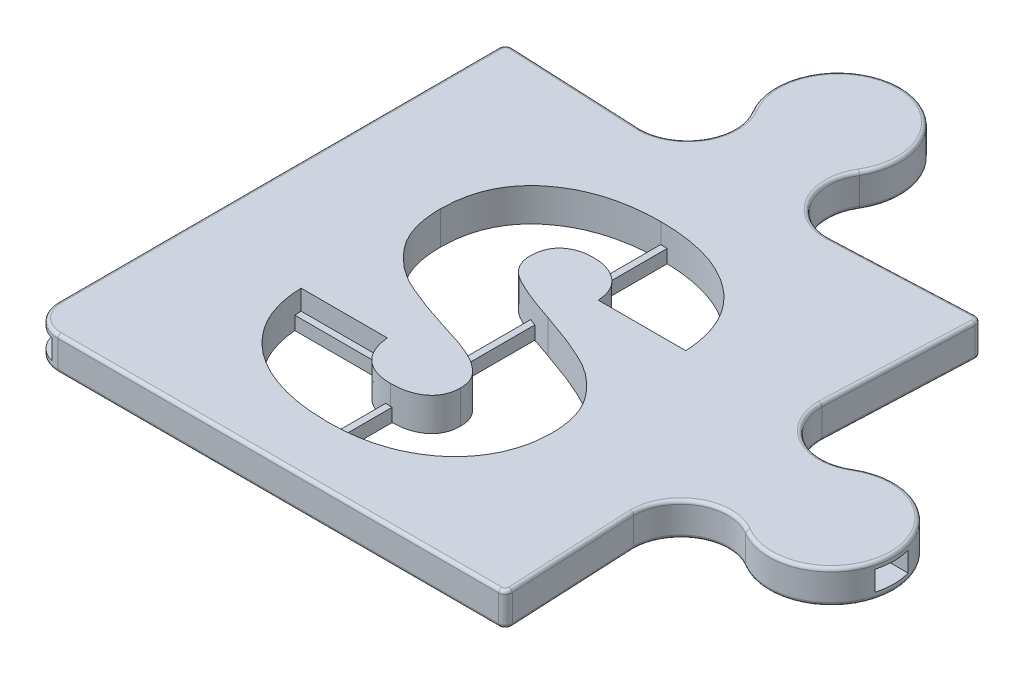
SolidWorks part; units mm, degrees
ref_plane "Front Plane" through (0, 0, 0) normal (0, 0, 1) x (1, 0, 0)
ref_plane "Top Plane" through (0, 0, 0) normal (0, 1, 0) x (1, 0, 0)
ref_plane "Right Plane" through (0, 0, 0) normal (1, 0, 0) x (0, 0, -1)
sketch "Sketch1" plane through (0, 0, 0) normal (0, 1, 0) x (1, 0, 0)
  line L0 (-31, -36) -> (37, -36) construction
  line L1 (-36, 37) -> (-36, -31) construction
  line L2 (-14.1421, 36) -> (-36, 37) construction
  line L3 (37, 37) -> (14.1421, 36) construction
  line L4 (36, 13.1421) -> (37, 37) construction
  line L5 (37, -36) -> (36, -15.1421) construction
  line L6 (-35.4, 36.3719) -> (-35.4, -31)
  line L7 (-36, 36) -> (36, 36) construction
  line L8 (-36, 36) -> (-36, -36) construction
  line L9 (-36, -36) -> (36, -36) construction
  line L10 (36, 36) -> (36, -36) construction
  line L11 (-31, -35.4) -> (36.3705, -35.4)
  line L12 (36.3705, -35.4) -> (35.4, -15.1568)
  line L13 (35.4, 13.155) -> (36.3732, 36.372)
  line L14 (36.3732, 36.372) -> (14.1555, 35.4)
  line L15 (-14.1562, 35.4) -> (-35.4, 36.3719)
  line L16 (-30, -24) -> (30, -24) construction
  line L17 (-30, 29) -> (30, 29) construction
  line L18 (-30, 29) -> (-30, -31) construction
  line L19 (-30, -31) -> (30, -31) construction
  line L20 (30, 29) -> (30, -31) construction
  line L21 (-30, 24) -> (30, 24) construction
  line L22 (-30, 24) -> (-30, -26) construction
  line L23 (-30, -26) -> (30, -26) construction
  line L24 (30, 24) -> (30, -26) construction
  arc A0 (-36, -31) -> (-31, -36) centre (-31, -31) ccw construction
  arc A1 (-14.1421, 36) -> (-8.571, 45.8485) centre (-14.1421, 42.5) ccw construction
  arc A2 (8.571, 45.8485) -> (-8.571, 45.8485) centre (0, 51) ccw construction
  arc A3 (8.571, 45.8485) -> (14.1421, 36) centre (14.1421, 42.5) ccw construction
  arc A4 (36, 13.1421) -> (45.8485, 7.571) centre (42.5, 13.1421) ccw construction
  arc A5 (45.8485, -9.571) -> (45.8485, 7.571) centre (51, -1) ccw construction
  arc A6 (45.8485, -9.571) -> (36, -15.1421) centre (42.5, -15.1421) ccw construction
  arc A7 (-35.4, -31) -> (-31, -35.4) centre (-31, -31) ccw
  arc A8 (46.1576, -9.0567) -> (35.4, -15.1568) centre (42.5, -15.1421) ccw
  arc A9 (46.1576, -9.0567) -> (46.1576, 7.0567) centre (51, -1) ccw
  arc A10 (35.4, 13.155) -> (46.1576, 7.0567) centre (42.5, 13.1421) ccw
  arc A11 (8.0567, 46.1576) -> (14.1555, 35.4) centre (14.1421, 42.5) ccw
  arc A12 (8.0567, 46.1576) -> (-8.0567, 46.1576) centre (0, 51) ccw
  arc A13 (-14.1562, 35.4) -> (-8.0567, 46.1576) centre (-14.1421, 42.5) ccw
  point P32 (36, 0)
  point P34 (0, 36)
  dimension "D5" = 6.5
  dimension "D6" = 10
  dimension "D7" = 6.5
  dimension "D13" = 5
  dimension "D9" = 10
  dimension "D11" = 6.5
  dimension "D12" = 6.5
  dimension "D1" = 72
  dimension "D2" = 1
  dimension "D3" = 1
  dimension "D4" = 15
  dimension "D8" = 1
  dimension "D10" = 35
  dimension "D14" = 15
  dimension "D15" = 36
  dimension "D16" = 1
  dimension "D18" = 60
  dimension "D19" = 60
  dimension "D20" = 5
  dimension "D21" = 6
  dimension "D22" = 5
  dimension "D23" = 50
  dimension "D24" = 2
  dimension "D17" = 0.6
extrude "Boss-Extrude1" add sketch "Sketch1" along normal blind 5
sketch "Sketch6" plane through (0, 0, 0) normal (0, -1, 0) x (1, 0, 0)
  line L0 (-35.4, -36.3719) -> (-35.4, 31) construction
  line L1 (-35.4, 17.9) -> (-27.4, 17.9)
  line L2 (-35.4, 17.9) -> (-35.4, -16.1)
  line L3 (-35.4, -16.1) -> (-27.4, -16.1)
  line L4 (-27.4, 17.9) -> (-27.4, -16.1)
  line L5 (-31, 35.4) -> (36.3705, 35.4) construction
  line L6 (-35.4, 14.65) -> (-30.4, 14.65)
  line L7 (-35.4, 14.65) -> (-35.4, -12.85)
  line L8 (-35.4, -12.85) -> (-30.4, -12.85)
  line L9 (-30.4, 14.65) -> (-30.4, -12.85)
  point P15 (-27.4, 0.9)
  point P16 (-30.4, 0.9)
  line M28 (-35.4, 31) -> (-35.4, -36.3719)
  dimension "D1" = 8
  dimension "D2" = 20.75
  dimension "D3" = 27.5
  dimension "D4" = 5
  dimension "D5" = 34
extrude "Cut-Extrude3" cut sketch "Sketch6" against normal blind 3 from offset 1 contours L6 L9 L8 L3 L4 L1 M28 | L9 L6 L2 L8 region at (-29.8665, 0, 0.9) region at (-32.9, 0, 0.9) offset against normal yes
extrude "Cut-Extrude4" cut sketch "Sketch6<3>" against normal up to next contours L9 L6 L2 L8 region at (-32.9, 0, 0.9)
sketch "Sketch6<3>" plane through (0, 0, 0) normal (0, -1, 0) x (1, 0, 0) same geometry as "Sketch6"
sketch "Sketch8" plane through (0, 0, 0) normal (0, -1, 0) x (1, 0, 0)
  line L1 (-2.5, -51.4) -> (2.5, -51.4)
  line L2 (-2.5, -51.4) -> (-2.5, -60.4)
  line L3 (-2.5, -60.4) -> (2.5, -60.4)
  line L4 (2.5, -51.4) -> (2.5, -60.4)
  line L5 (51.4, 3.5) -> (60.4, 3.5)
  line L6 (51.4, 3.5) -> (51.4, -1.5)
  line L7 (51.4, -1.5) -> (60.4, -1.5)
  line L8 (60.4, 3.5) -> (60.4, -1.5)
  arc A0 (-8.0567, -46.1576) -> (8.0567, -46.1576) centre (0, -51) ccw construction
  arc A1 (46.1576, -7.0567) -> (46.1576, 9.0567) centre (51, 1) ccw construction
  point P4 (0, -60.4)
  point P13 (60.4, 1)
  dimension "D1" = 5
  dimension "D2" = 9
  dimension "D3" = 5
  dimension "D4" = 9
extrude "Cut-Extrude5" cut sketch "Sketch8" against normal blind 3 from offset 1 offset against normal yes
sketch "Sketch9" plane through (0, 0, 0) normal (0, -1, 0) x (1, 0, 0)
  line L0 (-31, 35.4) -> (36.3705, 35.4) construction
  line L1 (-35.4, 14.65) -> (-35.4, 31) construction
  line L2 (-31.7636, 35.3332) -> (-35.4, 31) construction
  line L3 (-33.2571, 29.735) -> (-30.0429, 33.565) construction
  line L4 (-30.0429, 33.565) -> (-33.2571, 29.735) construction
  line L5 (-30.0429, 33.565) -> (-32.7119, 35.8048)
  line L6 (-33.2571, 29.735) -> (-35.926, 31.9747)
  line L7 (-32.7119, 35.8048) -> (-35.926, 31.9747)
  circle A0 centre (-31.65, 31.65) radius 2.5
  arc A1 (-31, 35.4) -> (-35.4, 31) centre (-31, 31) ccw construction
  arc M41 (-31, 35.4) -> (-35.4, 31) centre (-31, 31) ccw
  dimension "D1" = 5
  dimension "D3" = 3.75
  dimension "D4" = 5.6569
  dimension "D2" = 3.75
extrude "Cut-Extrude6" cut sketch "Sketch9" against normal blind 3 from offset 1 contours A0 L5 L6 M41 | A0 L5 region at (-33.6239, 0, 33.3064) region at (-31.65, 0, 31.65) offset against normal yes
sketch "Sketch11" plane through (-35.4, 0, 0) normal (-1, 0, 0) x (0, 0, 1)
  line L0 (-13.155, 0) -> (-36.372, 0) construction
  line L1 (-25.1, 3) -> (-19.1, 3)
  line L2 (-25.1, 3) -> (-25.1, 1.5)
  line L3 (-25.1, 1.5) -> (-19.1, 1.5)
  line L4 (-19.1, 3) -> (-19.1, 1.5)
  line L5 (-16.1, 4) -> (-16.1, 1) construction
  line L6 (35.4, 0) -> (15.1568, 0) construction
  line L7 (20.9, 3) -> (26.9, 3)
  line L8 (20.9, 3) -> (20.9, 1.5)
  line L9 (20.9, 1.5) -> (26.9, 1.5)
  line L10 (26.9, 3) -> (26.9, 1.5)
  line L12 (17.9, 4) -> (17.9, 1) construction
  dimension "D1" = 3
  dimension "D2" = 1.5
  dimension "D3" = 3
  dimension "D4" = 6
  dimension "D5" = 3
  dimension "D6" = 1.5
  dimension "D7" = 6
  dimension "D8" = 3
fillet "Fillet1" radius 0.5 17 edges at (-35.4, 0, 22.825) (-34.1113, 0, 34.1113) (2.6853, 0, 35.4) (35.8853, 0, 25.2784) (38.9978, 0, 8.966) (60.4, 0, 1) (38.9986, 0, -6.9655) (35.8866, 0, -24.7635) (25.2643, 0, -35.886) (7.9657, 0, -38.9984) (0, 0, -60.4) (-7.9658, 0, -38.9981) (-24.7781, 0, -35.886) (-35.4, 0, -24.611) (-32.9, 0, -12.85) (-30.4, 0, 0.9) (-32.9, 0, 14.65)
fillet "Fillet2" radius 0.5 13 edges at (-7.9658, 5, -38.9981) (0, 5, -60.4) (7.9657, 5, -38.9984) (25.2643, 5, -35.886) (35.8866, 5, -24.7635) (38.9986, 5, -6.9655) (60.4, 5, 1) (38.9978, 5, 8.966) (35.8853, 5, 25.2784) (2.6853, 5, 35.4) (-34.1113, 5, 34.1113) (-35.4, 5, -2.686) (-24.7781, 5, -35.886)
fillet "Fillet3" radius 1 9 edges at (36.2202, 0.1464, -36.2187) (36.2202, 4.8536, -36.2187) (36.3732, 2.5, -36.372) (-35.2536, 0.1464, -36.2186) (-35.2536, 4.8536, -36.2186) (36.2169, 0.1464, 35.2536) (36.2169, 4.8536, 35.2536) (36.3705, 2.5, 35.4) (-35.4, 2.5, -36.3719)
extrude "Cut-Extrude9" cut sketch "Sketch11" against normal blind 3
chamfer "Chamfer1" distance 1 angle 50 2 edges at (-35.4, 1.5, 23.9) (-35.4, 1.5, -22.1) first distance on face at (-35.4, 2.25, -22.1)
sketch "Sketch12" plane through (0, 5, 0) normal (0, 1, 0) x (1, 0, 0)
  text T0 "S" font "Poppins" height 50
extrude "Cut-Extrude10" cut sketch "Sketch12" against normal through all
sketch "Sketch13" plane through (0, 0, 0) normal (0, -1, 0) x (1, 0, 0)
  line L0 (-31, 35.4) -> (35.3215, 35.4) construction
  line L1 (-0.4, 28.3462) -> (0.6, 28.3462)
  line L2 (-0.4, 28.3462) -> (-0.4, -25.6547)
  line L3 (-0.4, -25.6547) -> (0.6, -25.6547)
  line L4 (0.6, 28.3462) -> (0.6, -25.6547)
  line L5 (-34.9, 31) -> (-34.9, 15.15) construction
  line L7 (-18.7758, 11.0371) -> (-5.6541, 11.0371)
  line L8 (-18.7758, 11.0371) -> (-18.7758, 12.0371)
  line L9 (-18.7758, 12.0371) -> (-5.6541, 12.0371)
  line L10 (-5.6541, 11.0371) -> (-5.6541, 12.0371)
  line L11 (5.0281, -10.7585) -> (18.3326, -10.7585)
  line L12 (5.0281, -10.7585) -> (5.0281, -9.7585)
  line L13 (5.0281, -9.7585) -> (18.3326, -9.7585)
  line L14 (18.3326, -10.7585) -> (18.3326, -9.7585)
  spline S0 degree 3 poles (-5.812, 11.0371) (-5.7518, 11.4767) (-5.6367, 12.3175) (-5.2264, 13.4798) (-4.6563, 14.4815) (-3.9123, 15.3125) (-3.015, 15.9537) (-1.9902, 16.4176) (-0.8379, 16.6851) (-0.0289, 16.7184) (0.3916, 16.7358) knots 0 0 0 0 0.141573 0.2708 0.391372 0.508039 0.624489 0.741481 0.865633 1 1 1 1 construction
  spline S1 degree 3 poles (5.1628, -9.7585) (5.1226, -10.1425) (5.0447, -10.8849) (4.689, -11.9285) (4.1306, -12.8322) (3.3964, -13.5925) (2.5174, -14.2032) (1.5043, -14.6373) (0.3789, -14.9153) (-0.4139, -14.9396) (-0.8244, -14.9522) knots 0 0 0 0 0.13077 0.252828 0.370623 0.488556 0.609208 0.731394 0.860926 1 1 1 1 construction
  dimension "D1" = 1
  dimension "D2" = 54.0009
  dimension "D3" = 7.0538
  dimension "D4" = 34.5
  dimension "D5" = 1
  dimension "D6" = 1
extrude "Boss-Extrude2" add sketch "Sketch13" against normal blind 2
